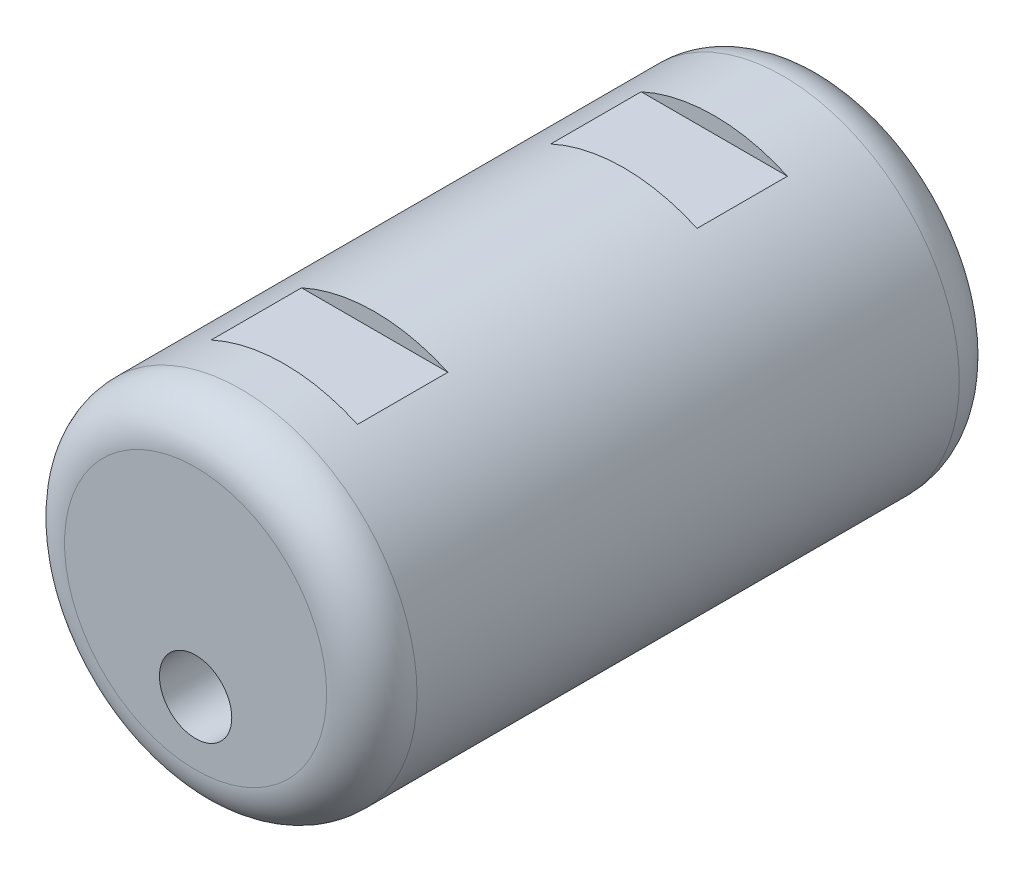
SolidWorks part; units mm, degrees
ref_plane "Front Plane" through (0, 0, 0) normal (0, 0, 1) x (1, 0, 0)
ref_plane "Top Plane" through (0, 0, 0) normal (0, 1, 0) x (1, 0, 0)
ref_plane "Right Plane" through (0, 0, 0) normal (1, 0, 0) x (0, 0, -1)
sketch "Sketch1" plane through (0, 0, 0) normal (0, 0, 1) x (1, 0, 0)
  circle A0 centre (0, 0) radius 3.9
  dimension "D1" = 7.8
extrude "Boss-Extrude1" add sketch "Sketch1" along normal blind 14
fillet "Fillet1" radius 1 2 edges at (3.9, 0, 14) (3.9, 0, 0)
sketch "Sketch2" plane through (0, 0, 14) normal (0, 0, 1) x (1, 0, 0)
  circle A0 centre (0, -1.5) radius 0.8
  dimension "D1" = 1.6
  dimension "D2" = 1.5
extrude "Cut-Extrude1" cut sketch "Sketch2" against normal blind 5
sketch "Sketch3" plane through (0, 0, 0) normal (0, 0, -1) x (-1, 0, 0)
  circle A0 centre (0, -1.5) radius 0.8
  dimension "D1" = 1.6
  dimension "D2" = 1.5
extrude "Cut-Extrude2" cut sketch "Sketch3" against normal blind 5
sketch "Sketch4" plane through (0, 0, 0) normal (1, 0, 0) x (0, 0, -1)
  line L0 (-1, 3.9) -> (-13, 3.9) construction
  line L1 (-2.5219, 3.9) -> (-4.5219, 3.9)
  line L2 (-2.5219, 3.9) -> (-2.5219, 3.5482)
  line L3 (-2.5219, 3.5482) -> (-4.5219, 3.5482)
  line L4 (-4.5219, 3.9) -> (-4.5219, 3.5482)
  dimension "D1" = 2
extrude "Cut-Extrude3" cut sketch "Sketch4" against normal blind 5 and the other way blind 5
sketch "Sketch5" plane through (0, 3.5482, 0) normal (0, 1, 0) x (1, 0, 0)
  circle A0 centre (0, -3.4744) radius 0.8
  dimension "D1" = 1.6
sketch "Sketch7" plane through (0, 0, 0) normal (1, 0, 0) x (0, 0, -1)
  line L0 (-4.5219, 3.5482) -> (-2.5219, 3.5482) construction
  line L1 (-12.0367, 4.9495) -> (-10.0367, 4.9495)
  line L2 (-12.0367, 4.9495) -> (-12.0367, 3.5482)
  line L3 (-12.0367, 3.5482) -> (-10.0367, 3.5482)
  line L4 (-10.0367, 4.9495) -> (-10.0367, 3.5482)
  line L5 (-12.0367, 4.9495) -> (-10.0367, 3.5482) construction
  line L6 (-12.0367, 3.5482) -> (-10.0367, 4.9495) construction
  line L7 (-4.5219, 3.5482) -> (-2.5219, 3.5482)
  point P4 (-11.0367, 4.2488)
  dimension "D1" = 2
extrude "Cut-Extrude4" cut sketch "Sketch7" against normal blind 10 and the other way blind 10 contours L4 L1 L2 L3 region at (0, 4.2488, 11.0367)
sketch "Sketch8" plane through (0, 3.5482, 0) normal (0, 1, 0) x (1, 0, 0)
  circle A0 centre (0, -11.005) radius 0.75
  dimension "D1" = 1.5
